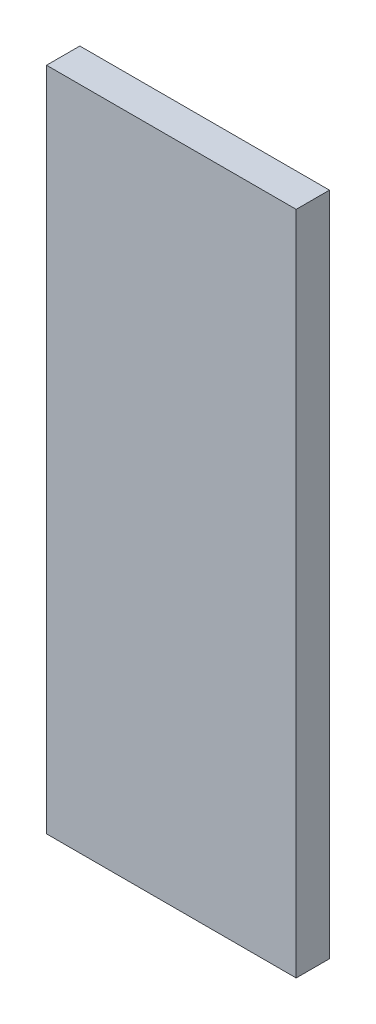
SolidWorks part; units mm, degrees
material "6061-T6 (SS)"
ref_plane "Alzado" through (0, 0, 0) normal (0, 0, 1) x (1, 0, 0)
ref_plane "Planta" through (0, 0, 0) normal (0, 1, 0) x (1, 0, 0)
ref_plane "Vista lateral" through (0, 0, 0) normal (1, 0, 0) x (0, 0, -1)
sketch "Sketch1" plane through (0, 0, 0) normal (0, 0, 1) x (1, 0, 0)
  line L1 (-15, 40) -> (15, 40)
  line L2 (-15, 40) -> (-15, -40)
  line L3 (-15, -40) -> (15, -40)
  line L4 (15, 40) -> (15, -40)
  line L5 (-15, 40) -> (15, -40) construction
  line L6 (-15, -40) -> (15, 40) construction
  point P0 (0, 0)
  dimension "D1" = 30
  dimension "D2" = 80
extrude "Boss-Extrude1" add sketch "Sketch1" along normal blind 4
sketch "Sketch2" plane through (0, 0, 4) normal (0, 0, 1) x (1, 0, 0)
  line L5 (15, 1.25) -> (0, 1.25)
  line L12 (15, -40) -> (15, 40) construction
  line L13 (0, 1.25) -> (0, -1.25)
  line L14 (0, -1.25) -> (15, -1.25)
  line L15 (15, -1.25) -> (15, 1.25)
  point P6 (0, 0)
  point P8 (0, 0)
  dimension "D1" = 2.5
extrude "Cut-Extrude1" [suppressed] cut sketch "Sketch2" against normal blind 10
fillet "Fillet1" [suppressed] radius 2
